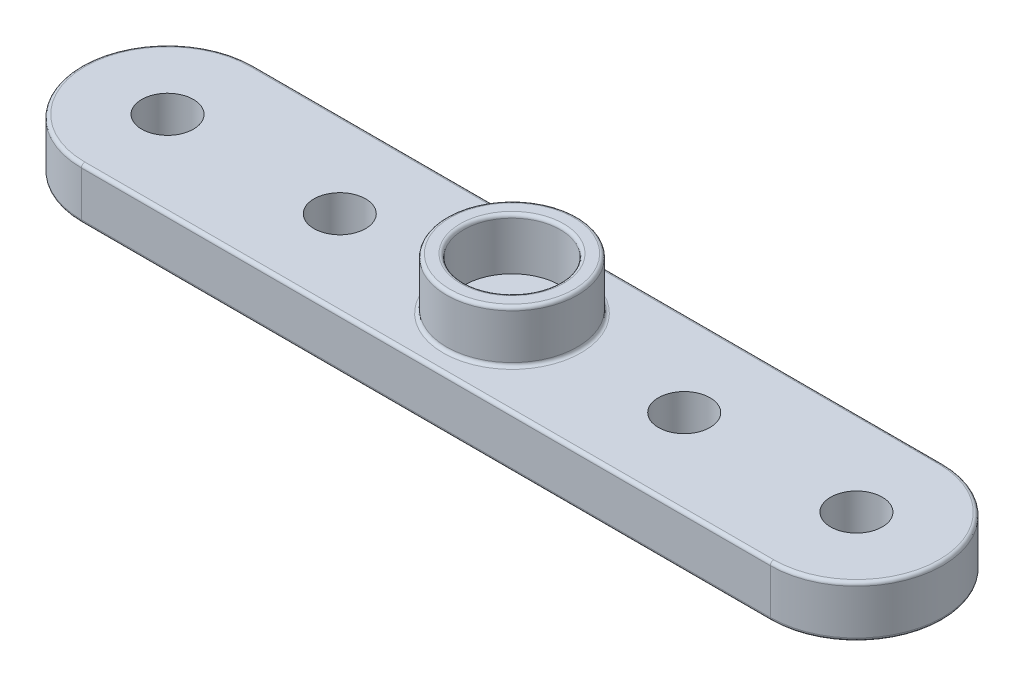
SolidWorks part; units mm, degrees
ref_plane "Front Plane" through (0, 0, 0) normal (0, 0, 1) x (1, 0, 0)
ref_plane "Top Plane" through (0, 0, 0) normal (0, 1, 0) x (1, 0, 0)
ref_plane "Right Plane" through (0, 0, 0) normal (1, 0, 0) x (0, 0, -1)
sketch "Sketch1" plane through (0, 0, 0) normal (0, 1, 0) x (1, 0, 0)
  line L0 (0, 5) -> (0, -5) construction
  line L1 (-25, 5) -> (25, 5)
  line L2 (-25, 5) -> (-25, -5)
  line L3 (-25, -5) -> (25, -5)
  line L4 (25, 5) -> (25, -5)
  line L6 (-25, 0) -> (25, 0) construction
  circle A0 centre (-20, 0) radius 1.5
  circle A1 centre (-10, 0) radius 1.5
  circle A2 centre (10, 0) radius 1.5
  circle A3 centre (20, 0) radius 1.5
  point P10 (0, 0)
  dimension "D3" = 3
  dimension "D1" = 10
  dimension "D2" = 50
  dimension "D4" = 10
  dimension "D5" = 10
extrude "Boss-Extrude1" add sketch "Sketch1" along normal blind 3
fillet "Fillet2" 2 edges at (-25, 1.5, -5) (-25, 1.5, 5) type full round first side face at (0, 1.5, -5) second side face at (0, 1.5, 5) middle face at (-25, 1.5, 0)
fillet "Fillet3" 2 edges at (25, 1.5, 5) (25, 1.5, -5) type full round first side face at (2.5, 1.5, 5) second side face at (2.5, 1.5, -5) middle face at (25, 1.5, 0)
sketch "Sketch2" plane through (0, 3, 0) normal (0, 1, 0) x (1, 0, 0)
  circle A0 centre (0, 0) radius 2.8
  circle A1 centre (0, 0) radius 3.8
  dimension "D1" = 5.6
  dimension "D2" = 1
extrude "Boss-Extrude2" add sketch "Sketch2" along normal blind 3
fillet "Fillet4" radius 0.2 11 edges at (0, 6, 2.8) (0, 6, 3.8) (-25, 3, 0) (0, 3, -5) (25, 3, 0) (-25, 0, 0) (0, 0, -5) (25, 0, 0) (0, 3, 3.8) (0, 3, 5) (0, 0, 5)
